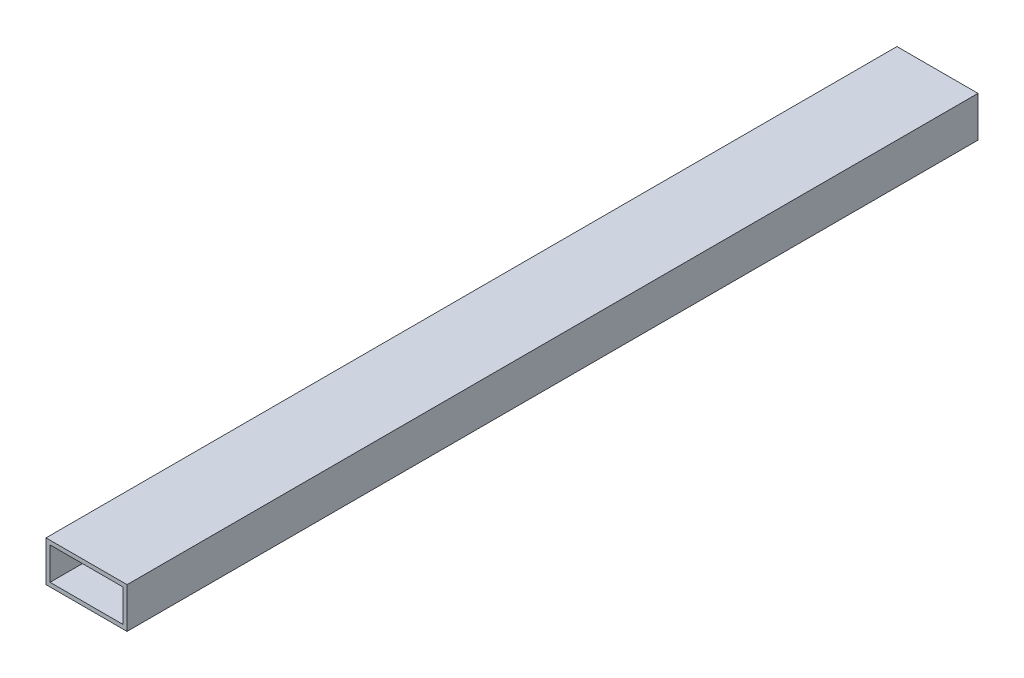
SolidWorks part; units mm, degrees
ref_plane "Front Plane" through (0, 0, 0) normal (0, 0, 1) x (1, 0, 0)
ref_plane "Top Plane" through (0, 0, 0) normal (0, 1, 0) x (1, 0, 0)
ref_plane "Right Plane" through (0, 0, 0) normal (1, 0, 0) x (0, 0, -1)
sketch "Sketch1" plane through (0, 0, 0) normal (0, 0, 1) x (1, 0, 0)
  line L1 (-25.4, -12.7) -> (25.4, -12.7)
  line L2 (-25.4, -12.7) -> (-25.4, 12.7)
  line L3 (-25.4, 12.7) -> (25.4, 12.7)
  line L4 (25.4, -12.7) -> (25.4, 12.7)
  line L5 (-25.4, -12.7) -> (25.4, 12.7) construction
  line L6 (-25.4, 12.7) -> (25.4, -12.7) construction
  line L7 (-22.86, -10.16) -> (22.86, -10.16)
  line L8 (-22.86, -10.16) -> (-22.86, 10.16)
  line L9 (-22.86, 10.16) -> (22.86, 10.16)
  line L10 (22.86, -10.16) -> (22.86, 10.16)
  line L11 (-22.86, -10.16) -> (22.86, 10.16) construction
  line L12 (-22.86, 10.16) -> (22.86, -10.16) construction
  point P0 (0, 0)
  point P6 (0, 0)
  dimension "D1" = 50.8
  dimension "D2" = 25.4
  dimension "D3" = 2.54
  dimension "D4" = 2.54
extrude "Boss-Extrude1" add sketch "Sketch1" against normal blind 533.4
